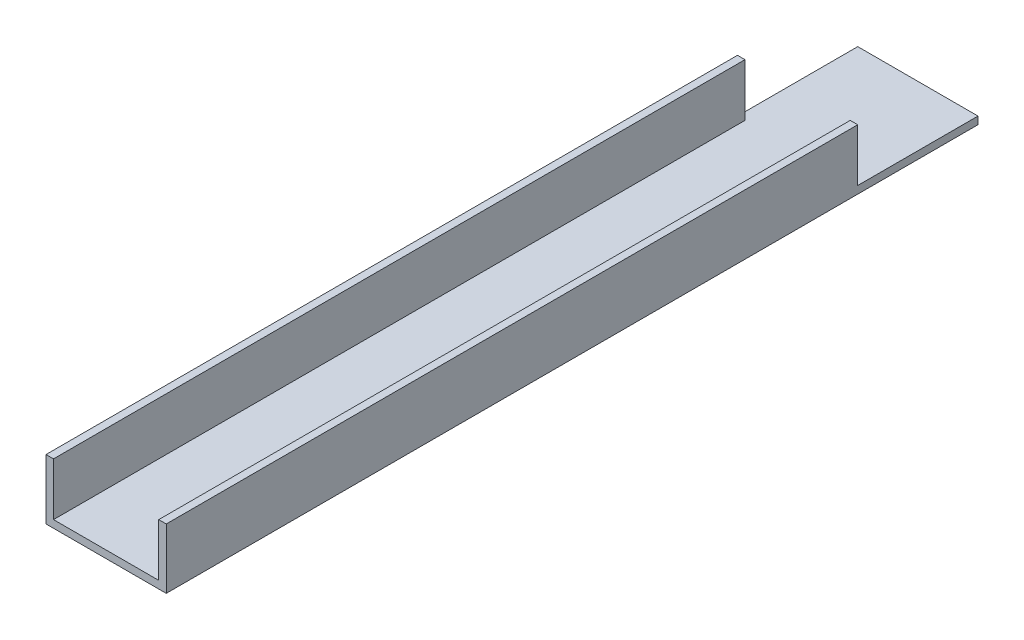
SolidWorks part; units mm, degrees
material "6063-T6"
ref_plane "Front" through (0, 0, 0) normal (0, 0, 1) x (1, 0, 0)
ref_plane "Top" through (0, 0, 0) normal (0, 1, 0) x (1, 0, 0)
ref_plane "Right" through (0, 0, 0) normal (1, 0, 0) x (0, 0, -1)
sketch "Sketch1" plane through (0, 0, 0) normal (0, 0, 1) x (1, 0, 0)
  line L0 (3.175, 3.175) -> (3.175, 25.4)
  line L1 (0, 0) -> (50.8, 0)
  line L2 (0, 0) -> (0, 25.4)
  line L4 (50.8, 0) -> (50.8, 25.4)
  line L5 (3.175, 3.175) -> (47.625, 3.175)
  line L6 (47.625, 3.175) -> (47.625, 25.4)
  line L7 (0, 25.4) -> (3.175, 25.4)
  line L8 (50.8, 25.4) -> (47.625, 25.4)
  dimension "D1" = 25.4
  dimension "D2" = 50.8
  dimension "D3" = 3.175
extrude "Boss-Extrude1" add sketch "Sketch1" along normal blind 342.9
sketch "Sketch2" plane through (0, 25.4, 0) normal (0, 1, 0) x (1, 0, 0)
  line L0 (0, -342.9) -> (0, 0) construction
  line L1 (50.8, 0) -> (0, 0)
  line L2 (50.8, 0) -> (50.8, -50.8)
  line L3 (50.8, -50.8) -> (0, -50.8)
  line L4 (0, 0) -> (0, -50.8)
  line L5 (50.8, 0) -> (0, -50.8) construction
  line L6 (50.8, -50.8) -> (0, 0) construction
  point P4 (25.4, -25.4)
  dimension "D1" = 50.8
extrude "Cut-Extrude1" cut sketch "Sketch2" against normal up to surface (22.225 mm away) up to face at (25.4, 3.175, 171.45)
